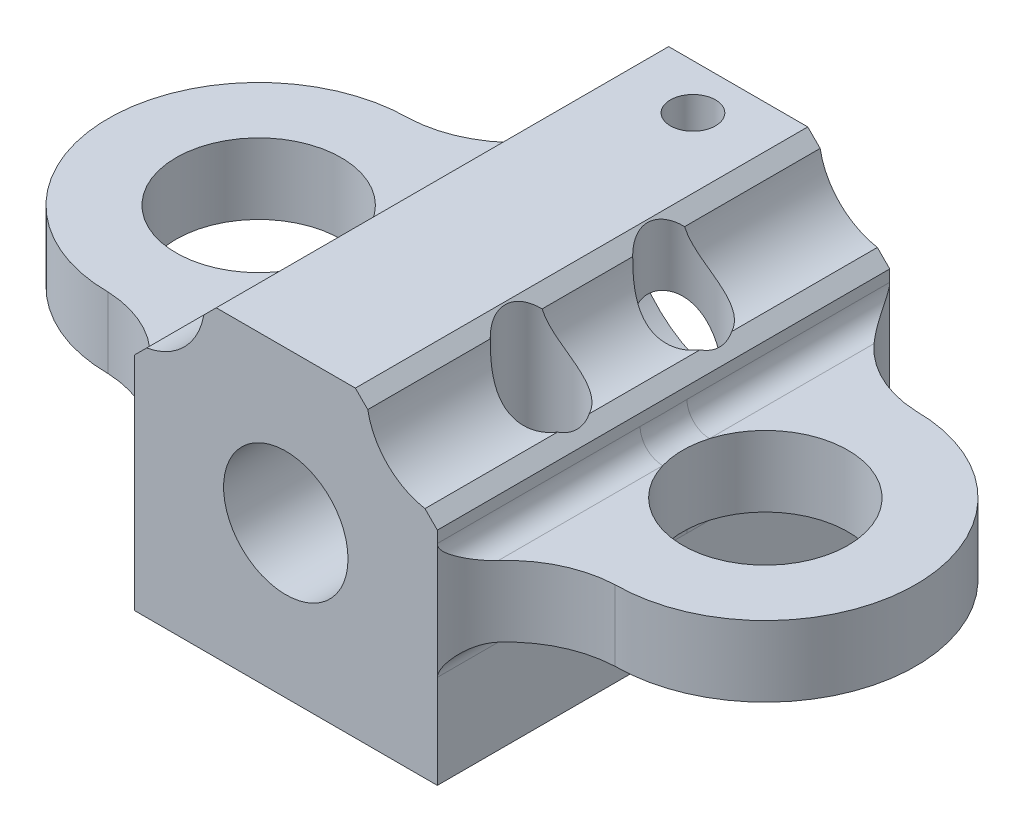
SolidWorks part; units mm, degrees
ref_plane "Front Plane" through (0, 0, 0) normal (0, 0, 1) x (1, 0, 0)
ref_plane "Top Plane" through (0, 0, 0) normal (0, 1, 0) x (1, 0, 0)
ref_plane "Right Plane" through (0, 0, 0) normal (1, 0, 0) x (0, 0, -1)
sketch "Sketch1" plane through (0, 0, 0) normal (0, 0, 1) x (1, 0, 0)
  line L0 (0, 0) -> (0, 69.4209) construction
  line L1 (8.509, 17.018) -> (-8.509, 17.018)
  line L2 (-8.509, 17.018) -> (-8.509, 0)
  line L3 (-8.509, 0) -> (8.509, 0)
  line L4 (8.509, 17.018) -> (8.509, 0)
  point P8 (0, 17.018)
  dimension "D1" = 17.018
  dimension "D2" = 17.018
extrude "Boss-Extrude1" add sketch "Sketch1" along normal blind 25.4
ref_plane "Plane1" through (0, 8.509, 0) normal (0, 1, 0) x (1, 0, 0)
sketch "Sketch2" plane through (0, 0, 0) normal (1, 0, 0) x (0, 0, -1)
  line L0 (-25.4, 8.509) -> (1.0345, 8.509) construction
  line L1 (-25.4, 0) -> (-25.4, 17.018) construction
  line L2 (-12.7, 14.859) -> (0, 14.859)
  line L3 (-12.7, 14.859) -> (-12.7, 12.0015)
  line L4 (-12.7, 12.0015) -> (-25.4, 12.0015)
  line L5 (-25.4, 12.0015) -> (-25.4, 8.509)
  line L6 (-25.4, 17.018) -> (0, 17.018) construction
  line L7 (-25.4, 8.509) -> (-12.1828, 8.509)
  line L9 (0, 0) -> (0, 17.018) construction
  line L10 (-12.1828, 8.509) -> (0, 8.509)
  line L11 (0, 8.509) -> (0, 14.859)
  dimension "D1" = 2.159
  dimension "D2" = 6.985
  dimension "D3" = 12.7
revolve "Cut-Revolve1" cut sketch "Sketch2" angle 360 about L7
sketch "Sketch4" plane through (0, 0, 0) normal (0, -1, 0) x (1, 0, 0)
  line L1 (-6, 17.0663) -> (6, 17.0663) construction
  line L2 (-6, 17.0663) -> (-6, 9.0663) construction
  line L3 (-6, 9.0663) -> (6, 9.0663) construction
  line L4 (6, 17.0663) -> (6, 9.0663) construction
  line L5 (-6, 17.0663) -> (6, 9.0663) construction
  line L6 (-6, 9.0663) -> (6, 17.0663) construction
  line L15 (-8.509, 25.4) -> (8.509, 25.4) construction
  circle A0 centre (-6, 17.0663) radius 1.016
  circle A1 centre (6, 17.0663) radius 1.016
  circle A2 centre (6, 9.0663) radius 1.016
  circle A3 centre (-6, 9.0663) radius 1.016
  point P0 (0, 13.0663)
  point P13 (6.0106, 9.0663)
  point P15 (0, 0)
  point P16 (-6, 9.0382)
  dimension "D3" = 2.032
  dimension "D1" = 12
  dimension "D2" = 8
  dimension "D6" = 8.3337
  dimension "D4" = 2
  dimension "D5" = 2
extrude "Cut-Extrude2" cut sketch "Sketch4" against normal blind 40
sketch "Sketch5" plane through (0, 8.509, 0) normal (0, 1, 0) x (1, 0, 0)
  line L1 (-14.1338, -12.7) -> (28.118, -12.7) construction
  line L5 (14.224, -12.7) -> (20.4143, -25.9751) construction
  line L8 (8.509, 0) -> (8.509, -25.4)
  line L10 (0, -25.4) -> (0, 11.748) construction
  line L11 (8.509, -25.4) -> (-8.509, -25.4) construction
  line L12 (14.224, 13.3789) -> (14.224, -38.7789) construction
  arc A0 (14.224, -4.2545) -> (14.224, -21.1455) centre (14.224, -12.7) cw
  circle A1 centre (14.224, -12.7) radius 4.6355
  arc A2 (14.224, -21.1455) -> (8.509, -25.4) centre (14.5055, -27.4893) ccw
  arc A3 (14.224, -4.2545) -> (8.509, 0) centre (14.5055, 2.0893) cw
  dimension "D2" = 9.271
  dimension "D4" = 3.81
  dimension "D3" = 6.35
  dimension "D1" = 5.715
  dimension "D5" = 25
extrude "Boss-Extrude2" add sketch "Sketch5" against normal blind 1.9844 and the other way blind 1.9844
mirror "Mirror1" about plane through (0, 0, 0) normal (1, 0, 0) of "Boss-Extrude2"
sketch "Sketch7" plane through (0, 0, 25.4) normal (0, 0, 1) x (1, 0, 0)
  line L0 (0, 19.0675) -> (0, -3.3693) construction
  circle A0 centre (8.509, 17.018) radius 3.9687
  circle A1 centre (-8.509, 17.018) radius 3.9687
  dimension "D1" = 7.9375
extrude "Cut-Extrude3" cut sketch "Sketch7" against normal through all
fillet "Fillet3" radius 1.27 4 edges
chamfer "Chamfer1" distance 0.635 angle 45 4 edges at (8.509, 13.0492, 12.7) (4.5402, 17.018, 12.7) (-4.5402, 17.018, 12.7) (-8.509, 13.0492, 12.7)
sketch "Sketch10" plane through (0, 17.018, 0) normal (0, 1, 0) x (1, 0, 0)
  line L0 (0, -9.0663) -> (0, -21.1529) construction
  line L1 (-6, -9.0663) -> (6, -9.0663) construction
  line L2 (-6, -9.0663) -> (-6, -17.0663) construction
  line L3 (-6, -17.0663) -> (6, -17.0663) construction
  line L4 (6, -9.0663) -> (6, -17.0663) construction
  line L5 (6, -13.0663) -> (-11.7995, -13.0663) construction
  circle A0 centre (6, -9.0663) radius 2.0193
  circle A1 centre (-6, -9.0663) radius 2.0193
  circle A2 centre (6, -17.0663) radius 2.0193
  circle A3 centre (-6, -17.0663) radius 2.0193
  dimension "D1" = 4.0386
extrude "Cut-Extrude6" cut sketch "Sketch10" against normal blind 13.97
sketch "Sketch11" plane through (0, 17.018, 0) normal (0, 1, 0) x (1, 0, 0)
  line L0 (6, -9.0663) -> (6, -28.9543) construction
ref_plane "Plane2" through (6, 0, 0) normal (1, 0, 0) x (0, 0, -1)
ref_plane "Plane3" through (0, 8.509, 0) normal (0, 1, 0) x (1, 0, 0)
sketch "Sketch12" plane through (0, 17.018, 0) normal (0, 1, 0) x (1, 0, 0)
  line L0 (3.9053, 0) -> (-3.9053, 0) construction
  circle A0 centre (0, -2.54) radius 1.2662
  dimension "D1" = 2.5324
  dimension "D2" = 2.54
extrude "Cut-Extrude7" cut sketch "Sketch12" against normal blind 2.54
